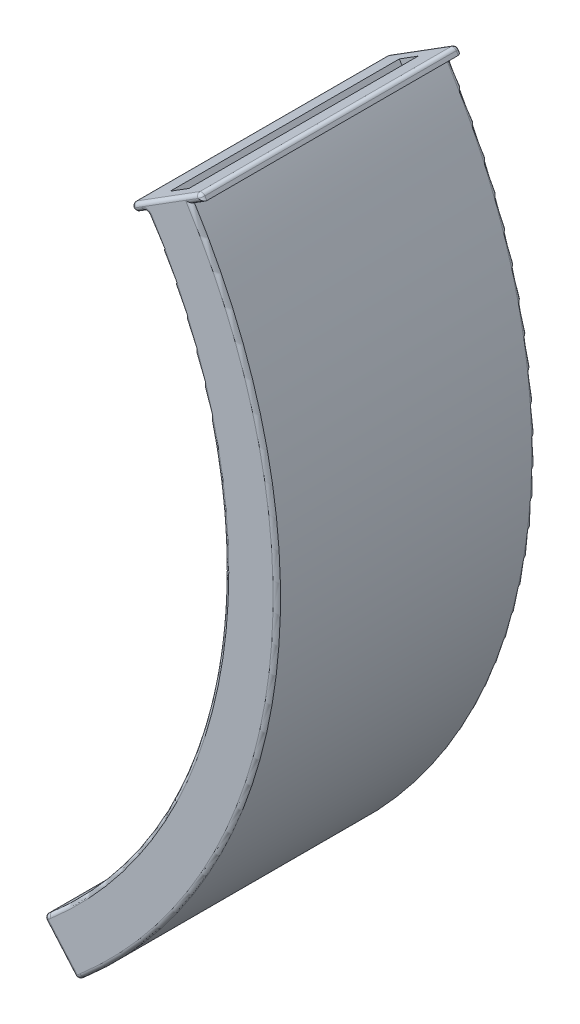
SolidWorks part; units mm, degrees
ref_plane "Front Plane" through (0, 0, 0) normal (0, 0, 1) x (1, 0, 0)
ref_plane "Top Plane" through (0, 0, 0) normal (0, 1, 0) x (1, 0, 0)
ref_plane "Right Plane" through (0, 0, 0) normal (1, 0, 0) x (0, 0, -1)
ref_plane "Plane1" through (-17.5, 0, 0) normal (1, 0, 0) x (0, 0, -1)
ref_plane "Plane2" through (-35, 0, 0) normal (1, 0, 0) x (0, 0, -1)
sketch "Sketch1" plane through (-17.5, 0, 0) normal (1, 0, 0) x (0, 0, -1)
  line L0 (0, 0) -> (0, -50) construction
  dimension "D1" = 50
sketch "Sketch2" plane through (0, 0, 0) normal (1, 0, 0) x (0, 0, -1)
  point P0 (0, 0)
sketch "Sketch3" plane through (-35, 0, 0) normal (1, 0, 0) x (0, 0, -1)
  point P0 (0, 0)
sketch "Sketch4" plane through (0, 0, 0) normal (0, 0, 1) x (1, 0, 0)
  line L0 (-17.5, 0) -> (-17.5, -50) construction
  arc A0 (9.9992, -0.126) -> (-45, -0.1273) centre (-17.5, -17.4818) cw construction
  arc A1 (9.9992, -0.126) -> (3.7287, -42.1146) centre (-17.5, -17.4818) cw construction
  arc A2 (11.7239, 0.8866) -> (5.0823, -43.587) centre (-17.5, -17.4818) cw construction
  dimension "D1" = 10
  dimension "D3" = 32.5182
  dimension "D4" = 46.2567
  dimension "D5" = 2
  dimension "D7" = 48.972
  dimension "D2" = 10
  dimension "D6" = 2
sketch "Sketch6" plane through (0, 0, 0) normal (0, 0, 1) x (1, 0, 0)
  line L0 (15.0182, 10) -> (15.0182, -39.6825) construction
  arc A0 (3.7287, -42.1146) -> (9.9992, -0.126) centre (-17.5, -17.4818) ccw construction
  dimension "D1" = 32.5182
ref_plane "Plane3" through (15.0182, 0, 0) normal (1, 0, 0) x (0, 0, -1)
sketch "Sketch7" plane through (0, 0, 0) normal (0, 0, 1) x (1, 0, 0)
  arc A0 (11.7239, 0.8866) -> (5.0823, -43.587) centre (-17.5, -17.4818) cw
sketch "Sketch8" plane through (0, 0, 0) normal (0, 0, 1) x (1, 0, 0)
  line L0 (17.0172, 0) -> (17.0172, -35.7055) construction
  arc A1 (5.0823, -43.587) -> (11.7239, 0.8866) centre (-17.5, -17.4818) ccw construction
ref_plane "Plane4" through (17.0172, 0, 0) normal (1, 0, 0) x (0, 0, -1)
sketch "Sketch9" plane through (17.0172, 0, 0) normal (1, 0, 0) x (0, 0, -1)
  line L0 (31.6795, -17.4818) -> (-12.7941, -17.4818) construction
  line L1 (0, 0.8866) -> (0, -43.587) construction
  dimension "D1" = 0
ref_plane "Plane5" through (0, -17.4818, 0) normal (0, 1, 0) x (1, 0, 0)
sketch "Sketch10" plane through (0, -17.4818, 0) normal (0, 1, 0) x (1, 0, 0)
  line L0 (17.0172, 31.6795) -> (17.0172, -12.7941) construction
  line L1 (17.0172, 8.75) -> (20.5172, 8.75)
  line L2 (17.0172, 8.75) -> (17.0172, -8.75)
  line L3 (17.0172, -8.75) -> (20.5172, -8.75)
  line L4 (20.5172, 8.75) -> (20.5172, -8.75)
  line L5 (5.0823, 0) -> (17.0172, 0) construction
  dimension "D1" = 17.5
  dimension "D2" = 3.5
  dimension "D3" = 8.75
sweep "Sweep1" add profiles "Sketch10" path "Sketch7"
shell "Shell1" thickness 1
sketch "Sketch11" plane through (2.9206, -4.6466, 0) normal (-0.5322, 0.8466, 0) x (0.8466, 0.5322, 0)
  line L0 (10.3978, -8.75) -> (13.8978, -8.75) construction
  line L1 (14.8978, 8.75) -> (9.3978, 8.75)
  line L2 (14.8978, 8.75) -> (14.8978, -8.75)
  line L3 (14.8978, -8.75) -> (9.3978, -8.75)
  line L4 (9.3978, 8.75) -> (9.3978, -8.75)
  line L5 (12.8978, 7.75) -> (11.3978, 7.75)
  line L6 (12.8978, 7.75) -> (12.8978, -7.75)
  line L7 (12.8978, -7.75) -> (11.3978, -7.75)
  line L8 (11.3978, 7.75) -> (11.3978, -7.75)
  line L9 (13.8978, -8.75) -> (13.8978, 8.75) construction
  dimension "D1" = 17.5
  dimension "D2" = 5.5
  dimension "D3" = 0
  dimension "D4" = 1
extrude "Boss-Extrude1" add sketch "Sketch11" along normal blind 0.5
sketch "Sketch12" plane through (-18.6595, -16.1414, 0) normal (-0.7563, -0.6542, 0) x (0, 0, 1)
  line L0 (-7.75, -37.2895) -> (7.75, -37.2895) construction
  line L1 (-8.75, -36.2895) -> (8.75, -36.2895)
  line L2 (-8.75, -36.2895) -> (-8.75, -39.7895)
  line L3 (-8.75, -39.7895) -> (8.75, -39.7895)
  line L4 (8.75, -36.2895) -> (8.75, -39.7895)
  line L5 (-8.75, -37.6395) -> (8.75, -37.6395)
  line L6 (-8.75, -37.6395) -> (-8.75, -38.4395)
  line L7 (-8.75, -38.4395) -> (8.75, -38.4395)
  line L8 (8.75, -37.6395) -> (8.75, -38.4395)
  line L10 (-8.75, -36.2895) -> (8.75, -36.2895)
  line L11 (-8.75, -36.2895) -> (-8.75, -37.6395)
  line L12 (-8.75, -37.6395) -> (8.75, -37.6395)
  line L13 (8.75, -36.2895) -> (8.75, -37.6395)
  line L14 (8.75, -39.7895) -> (-8.75, -39.7895)
  line L15 (8.75, -39.7895) -> (8.75, -38.4395)
  line L16 (8.75, -38.4395) -> (-8.75, -38.4395)
  line L17 (-8.75, -39.7895) -> (-8.75, -38.4395)
  line M3 (-7.75, -38.7895) -> (-7.75, -37.2895)
  line M4 (-7.75, -37.2895) -> (7.75, -37.2895)
  line M5 (7.75, -37.2895) -> (7.75, -38.7895)
  line M6 (7.75, -38.7895) -> (-7.75, -38.7895)
  line M7 (8.75, -36.2895) -> (-8.75, -36.2895)
  line M8 (-8.75, -36.2895) -> (-8.75, -39.7895)
  line M9 (-8.75, -39.7895) -> (8.75, -39.7895)
  line M10 (8.75, -39.7895) -> (8.75, -36.2895)
  dimension "D1" = 0.8
  dimension "D2" = 0.35
extrude "Boss-Extrude2" add sketch "Sketch12" along normal blind 0.5 contours L7 M8 M9 M10 M5 M6 M3 | L7 M3 M6 M5 | L5 L4 M8 M3 M4 M5 M7 | L5 M3 M5 M4 | L7 L4 L5 M5 | L2 L7 L5 M3
fillet "Fillet1" radius 0.25 26 edges at (16.6386, -22.5801, -8.75) (16.6386, -22.5801, 8.75) (20.1002, -23.097, 8.75) (20.1002, -23.097, -8.75) (15.2677, 3.7046, 0) (12.9394, 2.2412, -8.75) (10.6112, 0.7778, 0) (12.9394, 2.2412, 8.75) (15.4008, 3.493, 8.75) (15.1105, 3.0152, -8.75) (11.3006, 0.6205, -8.75) (15.4008, 3.493, -8.75) (10.8772, 0.3544, 0) (10.7442, 0.5661, -8.75) (11.3006, 0.6205, 8.75) (15.1105, 3.0152, 8.75) (10.7442, 0.5661, 8.75) (11.7239, 0.8866, 0) (4.8932, -43.7505, 8.75) (4.8932, -43.7505, -8.75) (7.183, -46.3975, -8.75) (7.183, -46.3975, 8.75) (4.7041, -43.9141, 0) (5.849, -45.2376, -8.75) (6.9939, -46.5611, 0) (5.849, -45.2376, 8.75)
